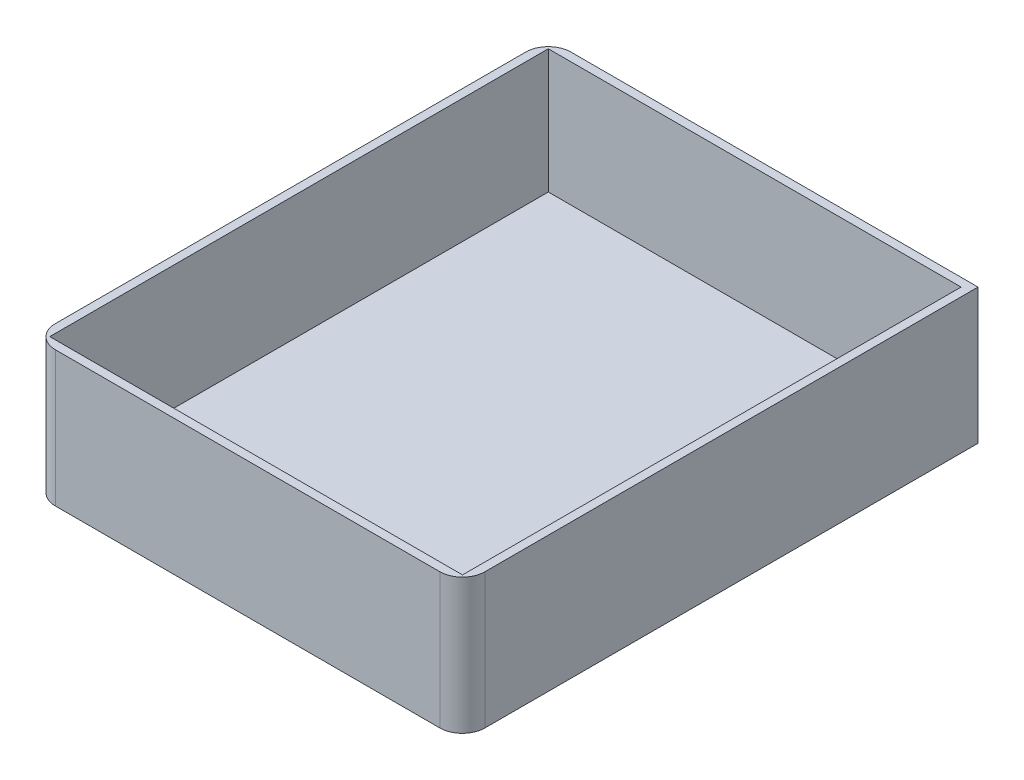
SolidWorks part; units mm, degrees
ref_plane "Front Plane" through (0, 0, 0) normal (0, 0, 1) x (1, 0, 0)
ref_plane "Top Plane" through (0, 0, 0) normal (0, 1, 0) x (1, 0, 0)
ref_plane "Right Plane" through (0, 0, 0) normal (1, 0, 0) x (0, 0, -1)
sketch "Sketch1" plane through (0, 0, 0) normal (0, 1, 0) x (1, 0, 0)
  line L1 (0, 0) -> (381, 0)
  line L2 (0, 0) -> (0, 457.2)
  line L3 (0, 457.2) -> (381, 457.2)
  line L4 (381, 0) -> (381, 457.2)
  line L5 (7.5, 7.6) -> (373.5, 7.6)
  line L6 (7.5, 7.6) -> (7.5, 449.7)
  line L7 (7.5, 449.7) -> (373.5, 449.7)
  line L8 (373.5, 7.6) -> (373.5, 449.7)
  dimension "D1" = 457.2
  dimension "D2" = 381
  dimension "D3" = 7.5
  dimension "D4" = 7.5
  dimension "D5" = 7.6
  dimension "D6" = 7.5
extrude "Boss-Extrude1" add sketch "Sketch1" along normal blind 120
sketch "Sketch2" plane through (0, 0, 0) normal (0, -1, 0) x (1, 0, 0)
  line L5 (7.5, -449.7) -> (373.5, -449.7)
  line L6 (7.5, -449.7) -> (7.5, -7.6)
  line L7 (7.5, -7.6) -> (373.5, -7.6)
  line L8 (373.5, -449.7) -> (373.5, -7.6)
extrude "Boss-Extrude2" add sketch "Sketch2" against normal blind 10
fillet "Fillet1" radius 20 3 edges at (0, 60, 0) (0, 60, -457.2) (381, 60, 0)
